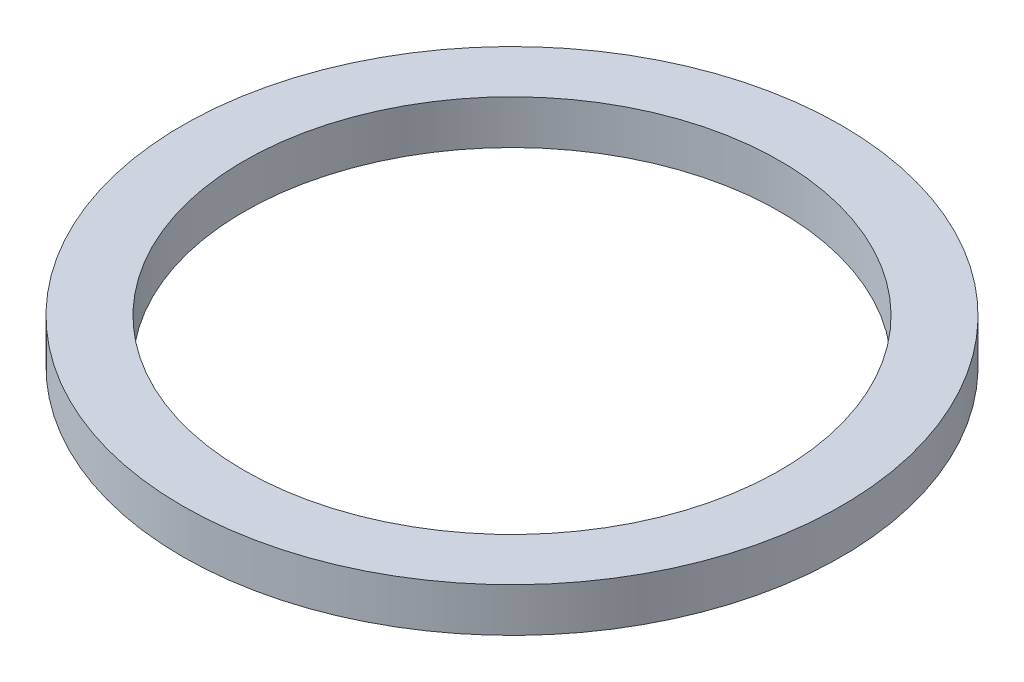
SolidWorks part; units mm, degrees
ref_plane "Front Plane" through (0, 0, 0) normal (0, 0, 1) x (1, 0, 0)
ref_plane "Top Plane" through (0, 0, 0) normal (0, 1, 0) x (1, 0, 0)
ref_plane "Right Plane" through (0, 0, 0) normal (1, 0, 0) x (0, 0, -1)
ref_axis "Axis1" through (0, 0, 0) along (0, 1, 0)
sketch "Sketch1" plane through (0, 0, 0) normal (0, 0, 1) x (1, 0, 0)
  line L0 (0, 0) -> (0, -4562.1687) construction
  line L2 (-7.5, 1) -> (-6.1, 1)
  line L3 (-7.5, 1) -> (-7.5, 0)
  line L4 (-7.5, 0) -> (-6.1, 0)
  line L5 (-6.1, 1) -> (-6.1, 0)
  point P7 (-7.2797, 1)
  dimension "D1" = 1
  dimension "D2" = 12.2
  dimension "D3" = 15
revolve "Revolve1" add sketch "Sketch1" angle 360 about L0
